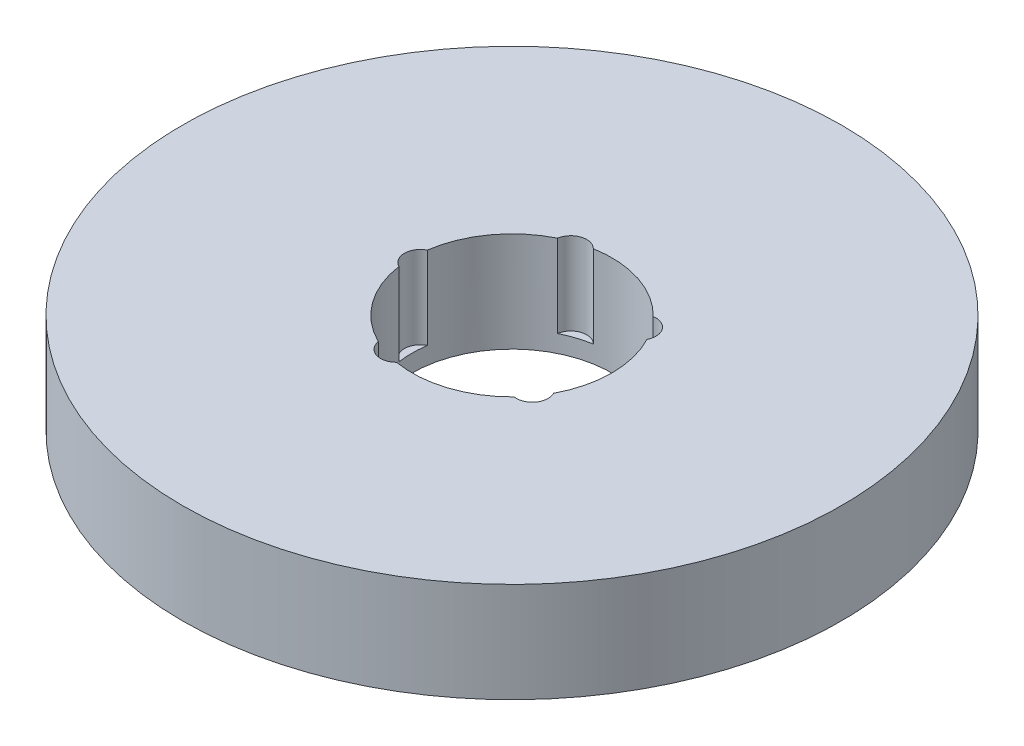
SolidWorks part; units mm, degrees
ref_plane "Front Plane" through (0, 0, 0) normal (0, 0, 1) x (1, 0, 0)
ref_plane "Top Plane" through (0, 0, 0) normal (0, 1, 0) x (1, 0, 0)
ref_plane "Right Plane" through (0, 0, 0) normal (1, 0, 0) x (0, 0, -1)
sketch "Sketch1" plane through (0, 0, 0) normal (0, 1, 0) x (1, 0, 0)
  circle A0 centre (0, 0) radius 82.5
  dimension "FLANGE_OD" = 165
extrude "Boss-Extrude1" add sketch "Sketch1" along normal blind 25
sketch "Sketch2" plane through (0, 0, 0) normal (0, 1, 0) x (1, 0, 0)
  circle A0 centre (0, 0) radius 25
  dimension "BORE_D" = 50
extrude "Cut-Extrude1" cut sketch "Sketch2" along normal through all
sketch "Sketch3" plane through (0, 25, 0) normal (0, 1, 0) x (1, 0, 0)
  circle A0 centre (0, 0) radius 22.9397 construction
  circle A1 centre (-22.9397, 0) radius 3.9852
  dimension "BOLT_D" = 7.9703
  dimension "BOLT_PCD" = 45.8794
extrude "Cut-Extrude2" cut sketch "Sketch3" against normal blind 20.666
pattern_circular "CirPattern1" count 5 over 360 about axis through (0, 0, 0) along (0, 1, 0) of "Cut-Extrude2"
